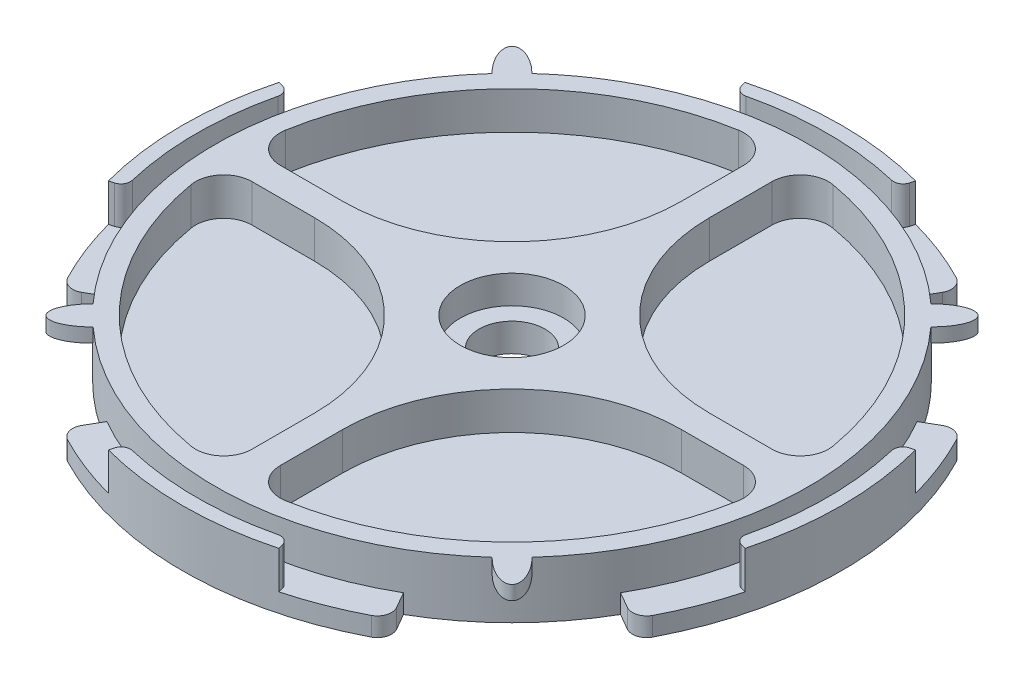
SolidWorks part; units mm, degrees
ref_plane "Front Plane" through (0, 0, 0) normal (0, 0, 1) x (1, 0, 0)
ref_plane "Top Plane" through (0, 0, 0) normal (0, 1, 0) x (1, 0, 0)
ref_plane "Right Plane" through (0, 0, 0) normal (1, 0, 0) x (0, 0, -1)
sketch "Sketch1" plane through (0, 0, 0) normal (0, 1, 0) x (1, 0, 0)
  circle A0 centre (0, 0) radius 35
  dimension "D1" = 70
extrude "Boss-Extrude1" add sketch "Sketch1" along normal blind 2
sketch "Sketch2" plane through (0, 2, 0) normal (0, 1, 0) x (1, 0, 0)
  circle A0 centre (0, 0) radius 31.5
  dimension "D1" = 63
extrude "Boss-Extrude2" add sketch "Sketch2" along normal blind 4
sketch "Sketch4" plane through (0, 2, 0) normal (0, 1, 0) x (1, 0, 0)
  circle A0 centre (0, 0) radius 35
  circle A1 centre (0, 0) radius 33.5
  circle A2 centre (0, 0) radius 35 construction
  dimension "D1" = 1.5
extrude "Boss-Extrude3" add sketch "Sketch4" along normal up to surface (4 mm away) up to face at (0, 6, 31.5)
sketch "Sketch5" plane through (0, 6, 0) normal (0, 1, 0) x (1, 0, 0)
  line L0 (0, 0) -> (35.9699, 35.9699) construction
  line L1 (0, 0) -> (60.1387, 0) construction
  line L2 (0, 0) -> (17.5, 30.3109) construction
  line L3 (0, 0) -> (30.3109, 17.5) construction
  line L4 (15.75, 27.2798) -> (17.5, 30.3109)
  line L5 (27.2798, 15.75) -> (30.3109, 17.5)
  arc A0 (27.2798, 15.75) -> (15.75, 27.2798) centre (0, 0) ccw
  circle A1 centre (0, 0) radius 31.5 construction
  arc A2 (30.3109, 17.5) -> (17.5, 30.3109) centre (0, 0) ccw
  circle A3 centre (0, 0) radius 35 construction
  dimension "D1" = 45
  dimension "D2" = 15
extrude "Cut-Extrude2" cut sketch "Sketch5" against normal through all
sketch "Sketch6" plane through (0, 6, 0) normal (0, 1, 0) x (1, 0, 0)
  line L0 (0, 0) -> (0, 44.9066) construction
  line L1 (0, 0) -> (49.8789, 0) construction
  line L2 (0, 0) -> (36.1286, 36.1286) construction
  line L3 (0, 0) -> (11.8027, 44.0484) construction
  line L4 (0, 0) -> (44.0484, 11.8027) construction
  line L5 (8.1528, 30.4267) -> (9.0587, 33.8074)
  line L6 (30.4267, 8.1528) -> (33.8074, 9.0587)
  arc A0 (33.8074, 9.0587) -> (9.0587, 33.8074) centre (0, 0) ccw
  arc A1 (30.4267, 8.1528) -> (8.1528, 30.4267) centre (0, 0) ccw
  arc A2 (15.75, 27.2798) -> (27.2798, 15.75) centre (0, 0) ccw construction
  arc A3 (17.5, 30.3109) -> (30.3109, 17.5) centre (0, 0) ccw construction
  dimension "D1" = 45
  dimension "D2" = 30
extrude "Cut-Extrude3" cut sketch "Sketch6" against normal up to surface (4 mm away) up to face at (-0.3915, 2, 0.3915)
sketch "Sketch7" plane through (0, 6, 0) normal (0, 1, 0) x (1, 0, 0)
  line L0 (0, 0) -> (0, 40.8739) construction
  line L1 (0, 0) -> (49.7748, 0) construction
  line L2 (0, 0) -> (33.072, 33.072) construction
  circle A0 centre (0, 0) radius 31.5 construction
  circle A1 centre (0, 0) radius 35 construction
  ellipse E0 centre (22.2739, 22.2739) end of major axis (24.7487, 24.7487) minor radius 1.5
  dimension "D1" = 45
  dimension "D2" = 3
extrude "Boss-Extrude4" add sketch "Sketch7" against normal blind 1.5
sketch "Sketch3" plane through (0, 6, 0) normal (0, 1, 0) x (1, 0, 0)
  line L0 (0, 0) -> (0, 37.6168) construction
  line L1 (0, 0) -> (43.5953, 0) construction
  line L2 (1.5, 1.5) -> (1.5, 29.4618)
  line L3 (1.5, 1.5) -> (29.4618, 1.5)
  arc A0 (29.4618, 1.5) -> (1.5, 29.4618) centre (0, 0) ccw
  circle A1 centre (0, 0) radius 31.5 construction
  dimension "D1" = 2
  dimension "D2" = 1.5
extrude "Cut-Extrude1" cut sketch "Sketch3" against normal up to surface (4 mm away) up to face at (10.892, 2, -10.892)
fillet "Fillet1" radius 18 1 edges at (1.5, 4, -1.5)
fillet "Fillet2" radius 3 2 edges at (29.4618, 4, -1.5) (1.5, 4, -29.4618)
fillet "Fillet3" radius 1.5 2 edges at (30.3109, 1, -17.5) (17.5, 1, -30.3109)
fillet "Fillet4" radius 1 2 edges at (8.6704, 4, -32.3585) (32.3585, 4, -8.6704)
pattern_circular "CirPattern1" count 4 over 360 about axis through (0, 6, 0) along (0, -1, 0) of "Cut-Extrude2", "Cut-Extrude3", "Boss-Extrude4", "Cut-Extrude1", "Fillet1", "Fillet2", "Fillet3", "Fillet4"
hole_wizard "CBORE for M6 Hex Socket Head Cap Screw1" positions "Sketch9" profile "Sketch8" counterbore size "M6" standard "ISO" end condition through all
sketch "Sketch9" plane through (0, 6, 0) normal (0, 1, 0) x (1, 0, 0)
  point P0 (0, 0)
sketch "Sketch8" plane through (0, 6, 0) normal (1, 0, 0) x (0, 0, 1)
  line L0 (0, 0) -> (0, 6)
  line L1 (0, 6) -> (3.5, 6)
  line L3 (3.5, 6) -> (3.5, 3)
  line L4 (3.5, 3) -> (5.5, 3)
  line L5 (5.5, 3) -> (5.5, 0)
  line L7 (5.5, 0) -> (0, 0)
  line L11 (0, -6.35) -> (0, 107.95) construction
  dimension "Thru Hole Dia." = 7
  dimension "Thru Hole Depth" = 6
  dimension "C'Bore Dia." = 11
  dimension "C'Bore Depth" = 3
fillet "Fillet5" [suppressed] radius 0.5
fillet "Fillet6" [suppressed] radius 0.5
fillet "Fillet7" [suppressed] radius 0.5
